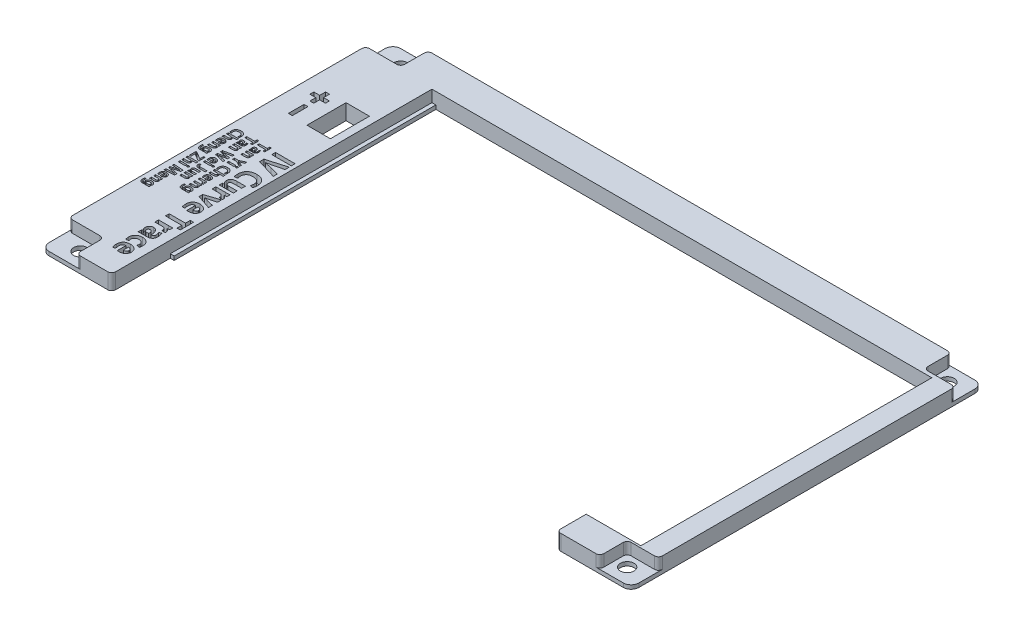
SolidWorks part; units mm, degrees
ref_plane "Front Plane" through (0, 0, 0) normal (0, 0, 1) x (1, 0, 0)
ref_plane "Top Plane" through (0, 0, 0) normal (0, 1, 0) x (1, 0, 0)
ref_plane "Right Plane" through (0, 0, 0) normal (1, 0, 0) x (0, 0, -1)
sketch "Sketch1" plane through (0, 0, 0) normal (0, 1, 0) x (1, 0, 0)
  line L1 (0, 0) -> (151, 0)
  line L2 (0, 0) -> (0, 90)
  line L3 (0, 90) -> (151, 90)
  line L4 (151, 0) -> (151, 90)
  dimension "D1" = 151
  dimension "D2" = 90
extrude "Boss-Extrude1" add sketch "Sketch1" along normal blind 4
sketch "Sketch2" plane through (0, 4, 0) normal (0, 1, 0) x (1, 0, 0)
  line L0 (151, 0) -> (151, 90) construction
  line L1 (151, 90) -> (0, 90) construction
  line L2 (0, 0) -> (151, 0) construction
  line L3 (0, 90) -> (0, 0) construction
  circle A0 centre (146, 86) radius 1.75
  circle A1 centre (146, 4) radius 1.75
  circle A2 centre (6, 86) radius 1.75
  circle A3 centre (6, 4) radius 1.75
  dimension "D1" = 3.5
  dimension "D2" = 5
  dimension "D3" = 4
  dimension "D4" = 3.5
  dimension "D5" = 5
  dimension "D6" = 4
  dimension "D7" = 4
  dimension "D8" = 6
  dimension "D9" = 3.5
  dimension "D10" = 3.5
  dimension "D11" = 6
  dimension "D12" = 4
extrude "Cut-Extrude1" cut sketch "Sketch2" against normal through all
fillet "Fillet1" radius 2 4 edges at (151, 2, -90) (151, 2, 0) (0, 2, 0) (0, 2, -90)
sketch "Sketch3" plane through (0, 4, 0) normal (0, 1, 0) x (1, 0, 0)
  line L0 (105, 62) -> (146, 62)
  line L1 (22, 82) -> (146, 82)
  line L2 (22, 82) -> (22, 62)
  line L3 (22, 62) -> (64, 62)
  line L4 (146, 82) -> (146, 62)
  line L6 (64, 62) -> (64, 43)
  line L7 (64, 43) -> (105, 43)
  line L8 (105, 62) -> (105, 43)
  line L9 (0, 88) -> (0, 2) construction
  line L10 (151, 2) -> (151, 88) construction
  line L11 (149, 90) -> (2, 90) construction
  line L12 (2, 0) -> (149, 0) construction
  line L13 (18, 0) -> (132, 0)
  line L14 (18, 0) -> (18, 15)
  line L15 (18, 15) -> (88, 15)
  line L16 (132, 0) -> (132, 15)
  line L17 (107, 15) -> (132, 15)
  line L19 (88, 15) -> (88, 29)
  line L20 (88, 29) -> (107, 29)
  line L21 (107, 15) -> (107, 29)
  dimension "D1" = 22
  dimension "D2" = 5
  dimension "D3" = 8
  dimension "D4" = 20
  dimension "D5" = 42
  dimension "D6" = 41
  dimension "D7" = 47
  dimension "D8" = 18
  dimension "D9" = 70
  dimension "D10" = 14
  dimension "D11" = 15
  dimension "D12" = 19
  dimension "D13" = 25
extrude "Cut-Extrude2" cut sketch "Sketch3" against normal through all
sketch "Sketch4" plane through (0, 4, 0) normal (0, 1, 0) x (1, 0, 0)
  line L0 (88, 15) -> (18, 15) construction
  line L1 (22, 82) -> (18, 82)
  line L2 (22, 82) -> (22, 62)
  line L3 (22, 15) -> (18, 15)
  line L4 (18, 82) -> (18, 15)
  line L5 (22, 62) -> (64, 62)
  line L7 (22, 15) -> (64, 15)
  line L8 (64, 62) -> (64, 43)
  line L9 (132, 0) -> (132, 15) construction
  line L10 (88, 15) -> (64, 15)
  line L11 (88, 15) -> (88, 29)
  line L12 (88, 43) -> (64, 43)
  line L15 (107, 29) -> (107, 15)
  line L16 (107, 15) -> (132, 15)
  line L18 (146, 62) -> (132, 62)
  line L19 (146, 62) -> (146, 7.5)
  line L20 (146, 7.5) -> (132, 7.5)
  line L21 (132, 15) -> (132, 7.5)
  line L23 (88, 43) -> (105, 43)
  line L25 (88, 29) -> (107, 29)
  line L27 (105, 62) -> (132, 62)
  line L28 (105, 62) -> (105, 43)
extrude "Cut-Extrude3" cut sketch "Sketch4" against normal through all contours L1 L4 L3 L7 L10 L11 L25 L15 L16 L21 L20 L19 L18 L27 L28 L23 L12 L8 L5 L2
sketch "Sketch5" plane through (18, 0, 0) normal (1, 0, 0) x (0, 0, -1)
  line L1 (82, 0) -> (15, 0)
  line L2 (82, 0) -> (82, 1)
  line L3 (82, 1) -> (15, 1)
  line L4 (15, 0) -> (15, 1)
  dimension "D1" = 67
  dimension "D2" = 1
extrude "Boss-Extrude2" add sketch "Sketch5" along normal blind 1
sketch "Sketch6" plane through (146, 0, 0) normal (-1, 0, 0) x (0, 0, 1)
  line L0 (-7.5, 0) -> (-82, 0) construction
  line L1 (-62, 0) -> (-7.5, 0)
  line L2 (-62, 0) -> (-62, 1)
  line L3 (-62, 1) -> (-7.5, 1)
  line L4 (-7.5, 0) -> (-7.5, 1)
  line L5 (-82, 0) -> (-82, 4) construction
  dimension "D1" = 1
  dimension "D2" = 20
  dimension "D3" = 54.5
extrude "Boss-Extrude3" add sketch "Sketch6" along normal blind 1
fillet "Fillet2" radius 1 2 edges at (132, 2, 0) (18, 2, 0)
sketch "Sketch7" plane through (0, 4, 0) normal (0, 1, 0) x (1, 0, 0)
  line L0 (18, 82) -> (18, 1) construction
  line L1 (10, 68) -> (16, 68)
  line L2 (10, 68) -> (10, 58)
  line L3 (10, 58) -> (16, 58)
  line L4 (16, 68) -> (16, 58)
  line L5 (149, 90) -> (2, 90) construction
  dimension "D1" = 10
  dimension "D2" = 6
  dimension "D3" = 2
  dimension "D4" = 22
extrude "Cut-Extrude4" cut sketch "Sketch7" against normal through all
sketch "Sketch8" plane through (0, 4, 0) normal (0, 1, 0) x (1, 0, 0)
  line L0 (10, 68) -> (10, 58) construction
  line L1 (5, 67.75) -> (6, 67.75)
  line L2 (5, 67.75) -> (5, 66.25)
  line L3 (5, 63.75) -> (6, 63.75)
  line L4 (6, 67.75) -> (6, 66.25)
  line L5 (3.5, 66.25) -> (5, 66.25)
  line L6 (3.5, 66.25) -> (3.5, 65.25)
  line L7 (3.5, 65.25) -> (5, 65.25)
  line L8 (7.5, 66.25) -> (7.5, 65.25)
  line L9 (5, 62.25) -> (6, 62.25)
  line L10 (5, 62.25) -> (5, 58.25)
  line L11 (5, 58.25) -> (6, 58.25)
  line L12 (6, 62.25) -> (6, 58.25)
  line L13 (16, 68) -> (10, 68) construction
  line L14 (10, 58) -> (16, 58) construction
  line L15 (6, 66.25) -> (7.5, 66.25)
  line L16 (5, 65.25) -> (5, 63.75)
  line L17 (6, 65.25) -> (6, 63.75)
  line L18 (6, 65.25) -> (7.5, 65.25)
  dimension "D1" = 4
  dimension "D2" = 1
  dimension "D3" = 4
  dimension "D4" = 1
  dimension "D5" = 1.5
  dimension "D6" = 2.5
  dimension "D7" = 0.25
  dimension "D8" = 1.5
  dimension "D9" = 4
  dimension "D10" = 1
  dimension "D11" = 0.25
  dimension "D12" = 4
extrude "Cut-Extrude5" cut sketch "Sketch8" against normal blind 3
sketch "Sketch9" plane through (0, 4, 0) normal (0, 1, 0) x (1, 0, 0)
  line L0 (12, 48.4251) -> (12, 8.4251) construction
  line L1 (18, 82) -> (18, 1) construction
  line L2 (8, 48.4251) -> (8, 27.9896) construction
  line L3 (4.8, 48.4251) -> (4.8, 27.9896) construction
  line L4 (1.6, 48.4251) -> (1.6, 18.4251) construction
  line L5 (10, 58) -> (16, 58) construction
  line L6 (0, 88) -> (0, 2) construction
  text T0 "<b>IV Curve Tracer</b>" font "@Adobe Gothic Std B" height 5
  text T1 "Tan Yi Cherng" font "@Adobe Gothic Std B" height 2.5
  text T2 "Tan Wei Jun" font "@Adobe Gothic Std B" height 2.5
  text T3 "Cheng Zhi Meng" font "@Adobe Gothic Std B" height 2.5
  dimension "D1" = 40
  dimension "D2" = 6
  dimension "D3" = 3.2
  dimension "D4" = 3.2
  dimension "D5" = 9.5749
  dimension "D6" = 9.5749
  dimension "D7" = 9.5749
  dimension "D8" = 9.5749
  dimension "D9" = 1.6
extrude "Cut-Extrude6" cut sketch "Sketch9" against normal blind 2
sketch "Sketch10" plane through (0, 4, 0) normal (0, 1, 0) x (1, 0, 0)
  line L0 (0, 88) -> (0, 2) construction
  line L1 (0, 7) -> (9, 7)
  line L2 (0, 7) -> (0, 0)
  line L3 (0, 0) -> (9, 0)
  line L4 (9, 7) -> (9, 0)
  line L5 (2, 0) -> (17, 0) construction
  line L6 (149, 90) -> (2, 90) construction
  line L7 (0, 90) -> (9, 90)
  line L8 (0, 90) -> (0, 83)
  line L9 (0, 83) -> (9, 83)
  line L10 (9, 90) -> (9, 83)
  line L11 (151, 2) -> (151, 88) construction
  line L12 (143, 90) -> (151, 90)
  line L13 (143, 90) -> (143, 83)
  line L14 (143, 83) -> (151, 83)
  line L15 (151, 90) -> (151, 83)
  line L16 (133, 0) -> (149, 0) construction
  line L17 (143, 7) -> (151, 7)
  line L18 (143, 7) -> (143, 0)
  line L19 (143, 0) -> (151, 0)
  line L20 (151, 7) -> (151, 0)
  circle A0 centre (6, 4) radius 1.75 construction
  circle A1 centre (6, 86) radius 1.75 construction
  circle A2 centre (146, 86) radius 1.75 construction
  circle A3 centre (146, 4) radius 1.75 construction
  dimension "D1" = 3
  dimension "D2" = 3
  dimension "D3" = 3
  dimension "D4" = 3
  dimension "D5" = 0
  dimension "D6" = 0
  dimension "D7" = 3
  dimension "D8" = 3
  dimension "D9" = 0
  dimension "D10" = 0
  dimension "D11" = 0
  dimension "D12" = 3
  dimension "D13" = 3
extrude "Cut-Extrude7" cut sketch "Sketch10" against normal blind 3
fillet "Fillet3" radius 1 12 edges at (151, 2.5, -83) (143, 2.5, -90) (143, 2.5, -83) (143, 2.5, 0) (143, 2.5, -7) (151, 2.5, -7) (0, 2.5, -83) (9, 2.5, -83) (9, 2.5, -90) (9, 2.5, 0) (9, 2.5, -7) (0, 2.5, -7)
